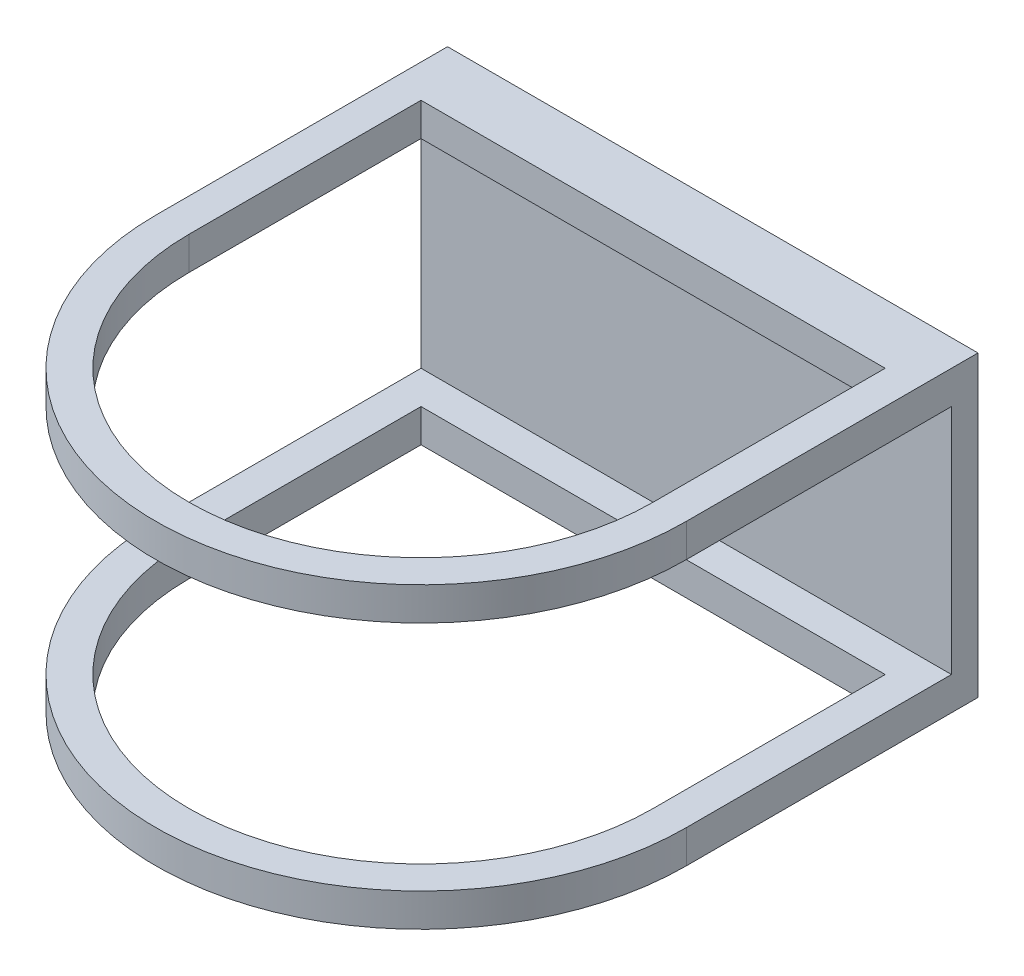
SolidWorks part; units mm, degrees
ref_plane "Front Plane" through (0, 0, 0) normal (0, 0, 1) x (1, 0, 0)
ref_plane "Top Plane" through (0, 0, 0) normal (0, 1, 0) x (1, 0, 0)
ref_plane "Right Plane" through (0, 0, 0) normal (1, 0, 0) x (0, 0, -1)
ref_plane "Plane1"
sketch "Sketch1" plane through (0, 0, 0) normal (0, 1, 0) x (-1, 0, 0)
  line L0 (50.8, -50.8) -> (-50.8, -50.8)
  line L1 (-50.8, -50.8) -> (-50.8, 0)
  line L2 (50.8, 0) -> (50.8, -50.8)
  line L3 (44.45, -44.45) -> (-44.45, -44.45)
  line L4 (-44.45, -44.45) -> (-44.45, 0)
  line L5 (44.45, 0) -> (44.45, -44.45)
  arc A0 (50.8, 0) -> (-50.8, 0) centre (0, 0) ccw
  arc A1 (44.45, 0) -> (-44.45, 0) centre (0, 0) ccw
  dimension "D5" = 44.45
  dimension "D1" = 101.6
  dimension "D2" = 6.35
  dimension "D3" = 6.35
  dimension "D4" = 6.35
  dimension "D6" = 44.45
extrude "Extrusion1" add sketch "Sketch1" along normal blind 6.35 contours L2 A0 L1 L0 A1 L5 L3 L4 region at (0, 0, -49.3632)
hole_wizard "Hole1" positions "Sketch3" profile "Sketch2" legacy
sketch "Sketch3" plane through (0, 0, -50.8) normal (0, 0, -1) x (-1, 0, 0)
  point P1 (-47.625, 3.175)
  point P2 (47.625, 3.175)
sketch "Sketch2" plane through (47.625, 3.175, -50.8) normal (1, 0, 0) x (0, 1, 0)
  line L0 (0, 0) -> (0, 25.4)
  line L1 (0, 25.4) -> (2.413, 25.4)
  line L2 (2.413, 25.4) -> (2.413, 0)
  line L3 (2.413, 0) -> (0, 0)
  line L4 (0, 110) -> (0, -10) construction
  dimension "Diameter" = 4.826
  dimension "Depth" = 25.4
ref_plane "Plane2" through (0, 0, 0) normal (0, 0, -1) x (-1, 0, 0)
ref_plane "Plane3" through (0, 0, 0) normal (1, 0, 0) x (0, 0, -1)
ref_axis "Axis1" through (0, -50, 0) along (0, 1, 0)
pattern_linear "Rectangular Pattern1" count 2 spacing 50.8 along (0, 1, 0) of bodies 102
ref_plane "Plane4" through (47.625, 53.975, -50.8) normal (0, 0, -1) x (-1, 0, 0)
hole_wizard "Hole2" positions "Sketch5" profile "Sketch4" legacy rebuild error yes
sketch "Sketch5" plane through (47.625, 53.975, -50.8) normal (0, 0, -1) x (-1, 0, 0)
  point P1 (0, 0)
  point P2 (95.25, 0)
sketch "Sketch4" plane through (47.625, 53.975, -50.8) normal (1, 0, 0) x (0, 1, 0)
  line L0 (0, 0) -> (0, 25.4)
  line L1 (0, 25.4) -> (2.413, 25.4)
  line L2 (2.413, 25.4) -> (2.413, 0)
  line L3 (2.413, 0) -> (0, 0)
  line L4 (0, 110) -> (0, -10) construction
  dimension "Diameter" = 4.826
  dimension "Depth" = 25.4
sketch "Sketch6" plane through (0, 0, -50.8) normal (0, 0, -1) x (-1, 0, 0)
  line L0 (-50.8, 57.15) -> (-50.8, 0)
  line L1 (-50.8, 0) -> (50.8, 0)
  line L2 (50.8, 0) -> (50.8, 57.15)
  line L3 (50.8, 57.15) -> (-50.8, 57.15)
  circle A0 centre (-47.625, 53.975) radius 2.413
  circle A1 centre (47.625, 53.975) radius 2.413
extrude "Extrusion3" add sketch "Sketch6" along normal blind 5.08
